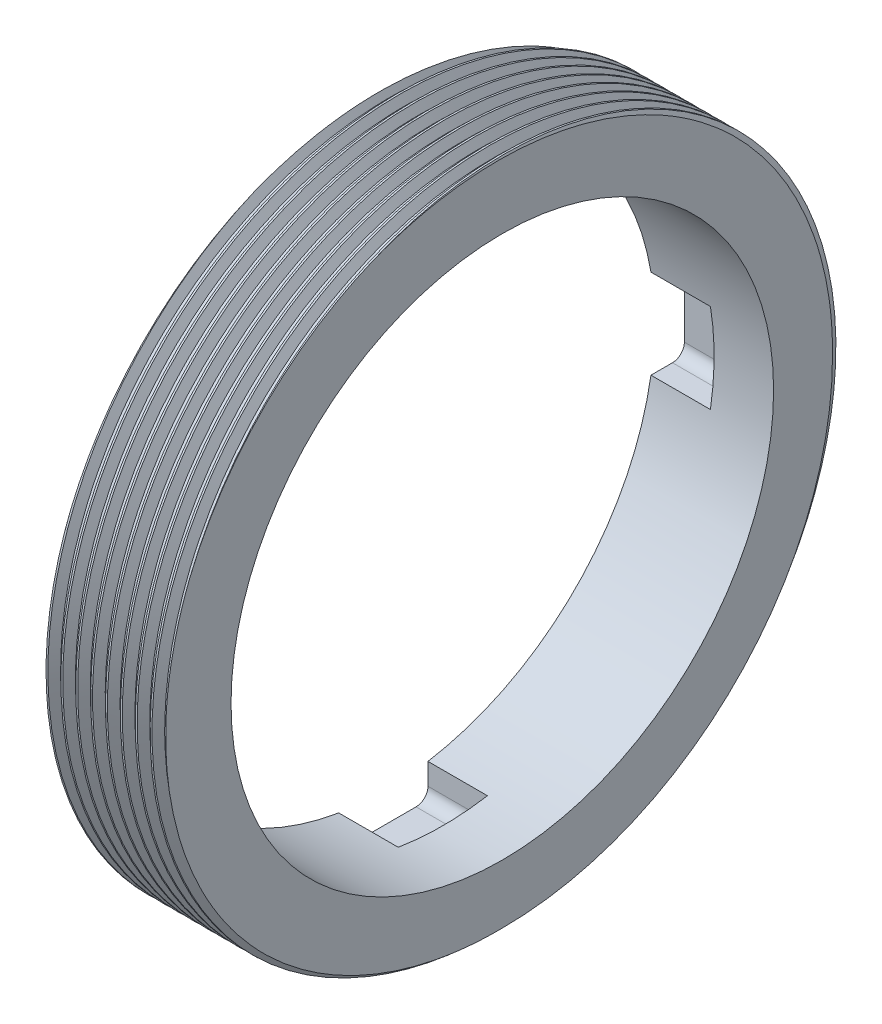
SolidWorks part; units mm, degrees
material "6061-T6 (SS)"
ref_plane "Front Plane" through (0, 0, 0) normal (0, 0, 1) x (1, 0, 0)
ref_plane "Top Plane" through (0, 0, 0) normal (0, 1, 0) x (1, 0, 0)
ref_plane "Right Plane" through (0, 0, 0) normal (1, 0, 0) x (0, 0, -1)
sketch "Sketch1" plane through (0, 0, 0) normal (0, 0, 1) x (1, 0, 0)
  line L0 (0, 28.956) -> (12.7, 28.956)
  line L1 (12.7, 28.956) -> (12.7, 35.2425)
  line L2 (12.7, 35.2425) -> (0, 35.2425)
  line L3 (0, 35.2425) -> (0, 28.956)
  line L4 (0, 0) -> (12.7, 0) construction
  dimension "D2" = 12.7
  dimension "D3" = 28.956
  dimension "D1" = 35.2425
revolve "Revolve1" add sketch "Sketch1" angle 360 about L4
sketch "Sketch2" plane through (0, 0, 0) normal (-1, 0, 0) x (0, 0, 1)
  line L0 (0, 0) -> (32.131, 0) construction
  line L1 (32.131, 3.4925) -> (32.131, -3.4925)
  line L2 (30.861, 4.7625) -> (0, 4.7625)
  line L3 (30.861, -4.7625) -> (0, -4.7625)
  line L4 (0, 4.7625) -> (0, -4.7625)
  arc A2 (32.131, 3.4925) -> (30.861, 4.7625) centre (30.861, 3.4925) ccw
  arc A3 (30.861, -4.7625) -> (32.131, -3.4925) centre (30.861, -3.4925) ccw
  point P7 (32.131, 0)
  dimension "D3" = 2.54
  dimension "D1" = 32.131
  dimension "D2" = 9.525
extrude "Cut-Extrude1" cut sketch "Sketch2" against normal blind 6.35
pattern_circular "CirPattern1" count 4 over 360 about axis through (0, 0, 0) along (-1, 0, 0) of "Cut-Extrude1"
thread "Thread1" pitch 1.5875 method extrude trim with start face yes trim with end face yes profile "Thread Profile1" start angle 180, offset 1.5875, length 0, pitch 1.5875, diameter 70.485
ref_plane "Plane1" through (14.2875, 0, -35.2425) normal (0, 1, 0) x (0, 0, -1)
sketch "Thread Profile1" plane through (14.2875, 0, -35.2425) normal (0, 1, 0) x (0, 0, -1)
  line L0 (0, 0) -> (0, 1.5875) construction
  line L1 (0, 0) -> (0.8593, 0.4961)
  line L2 (0.8593, 0.4961) -> (0.8593, 0.6945)
  line L3 (0.8593, 0.6945) -> (0, 1.1906)
  line L4 (0.8593, 0.5953) -> (0, 0.5953) construction
  line L11 (0, 0) -> (0, 1.1906)
  point P2 (0, 0)
  dimension "Pitch" = 1.5875
  dimension "Profile_Angle" = 60
  dimension "Profile_Land" = 0.1984
  dimension "Profile_Height" = 0.8593
equation "\"D3@Sketch1\"=2.28/2"
equation "\"D1@Sketch1\"=2.775/2"
equation "\"D7@Thread1\"=1/16in"
equation "\"D1@Sketch2\"=2.53/2"
